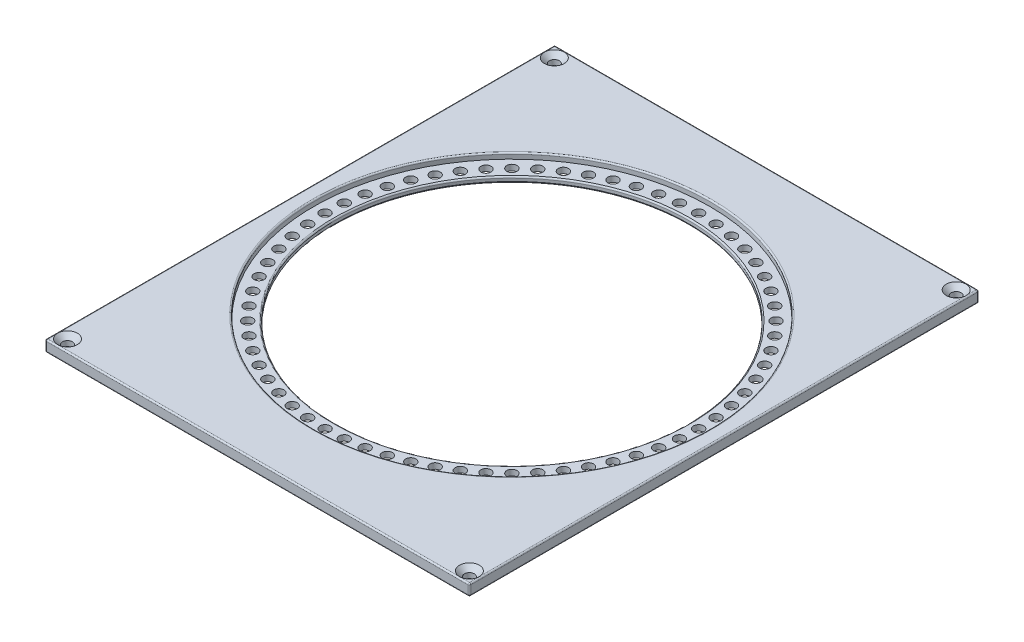
SolidWorks part; units mm, degrees
ref_plane "Front Plane" through (0, 0, 0) normal (0, 0, 1) x (1, 0, 0)
ref_plane "Top Plane" through (0, 0, 0) normal (0, 1, 0) x (1, 0, 0)
ref_plane "Right Plane" through (0, 0, 0) normal (1, 0, 0) x (0, 0, -1)
sketch "Sketch1" plane through (0, 0, 0) normal (0, 1, 0) x (1, 0, 0)
  line L0 (0, 0) -> (46.669, -46.669) construction
  line L1 (75, -90) -> (-75, -90)
  line L2 (75, -90) -> (75, 90)
  line L3 (75, 90) -> (-75, 90)
  line L4 (-75, -90) -> (-75, 90)
  line L5 (0, 90) -> (0, -90) construction
  line L6 (75, 0) -> (-75, 0) construction
  line L7 (0, 0) -> (36.6676, -54.877) construction
  line L8 (0, 0) -> (25.2571, -60.976) construction
  line L9 (0, 0) -> (12.876, -64.7318) construction
  line L10 (0, 0) -> (0, -66) construction
  line L11 (0, 0) -> (-12.876, -64.7318) construction
  line L12 (0, 0) -> (-25.2571, -60.976) construction
  line L13 (0, 0) -> (-36.6676, -54.877) construction
  line L14 (0, 0) -> (-46.669, -46.669) construction
  line L15 (0, 0) -> (-54.877, -36.6676) construction
  line L16 (0, 0) -> (-60.976, -25.2571) construction
  line L17 (0, 0) -> (-64.7318, -12.876) construction
  line L18 (0, 0) -> (-66, 0) construction
  line L19 (0, 0) -> (-64.7318, 12.876) construction
  line L20 (0, 0) -> (-60.976, 25.2571) construction
  line L21 (0, 0) -> (-54.877, 36.6676) construction
  line L22 (0, 0) -> (-46.669, 46.669) construction
  line L23 (0, 0) -> (-36.6676, 54.877) construction
  line L24 (0, 0) -> (-25.2571, 60.976) construction
  line L25 (0, 0) -> (-12.876, 64.7318) construction
  line L26 (0, 0) -> (0, 66) construction
  line L27 (0, 0) -> (12.876, 64.7318) construction
  line L28 (0, 0) -> (25.2571, 60.976) construction
  line L29 (0, 0) -> (36.6676, 54.877) construction
  line L30 (0, 0) -> (46.669, 46.669) construction
  line L31 (0, 0) -> (54.877, 36.6676) construction
  line L32 (0, 0) -> (60.976, 25.2571) construction
  line L33 (0, 0) -> (64.7318, 12.876) construction
  line L34 (0, 0) -> (66, 0) construction
  line L35 (0, 0) -> (64.7318, -12.876) construction
  line L36 (0, 0) -> (60.976, -25.2571) construction
  line L37 (0, 0) -> (54.877, -36.6676) construction
  line L38 (-75, 82) -> (-67, 82) construction
  line L39 (-67, 82) -> (-67, 90) construction
  line L40 (75, 82) -> (67, 82) construction
  line L41 (67, 82) -> (67, 90) construction
  line L42 (-75, -82) -> (-67, -82) construction
  line L43 (-67, -82) -> (-67, -90) construction
  line L44 (67, -90) -> (67, -82) construction
  line L45 (67, -82) -> (75, -82) construction
  line L46 (-67, 82) -> (-75, 90) construction
  line L47 (67, 82) -> (75, 90) construction
  line L48 (-67, -82) -> (-75, -90) construction
  line L49 (67, -82) -> (75, -90) construction
  line L50 (72.7, 87.7) -> (-72.7, 87.7) construction
  line L51 (46.669, -46.669) -> (42.4264, -42.4264) construction
  line L52 (-72.7, -87.7) -> (-72.7, 87.7) construction
  line L53 (72.7, -87.7) -> (-72.7, -87.7) construction
  line L54 (72.7, -87.7) -> (72.7, 87.7) construction
  line L55 (-72.7, 0) -> (-72.7, 10)
  line L56 (-72.7, 10) -> (-70.1478, 10)
  line L57 (-70.1478, 10) -> (-70.1478, -10)
  line L58 (-70.1478, -10) -> (-72.7, -10)
  line L59 (-72.7, -10) -> (-72.7, 0)
  line L60 (0, -87.7) -> (-10, -87.7)
  line L61 (-10, -87.7) -> (-10, -85.7)
  line L62 (-10, -85.7) -> (10, -85.7)
  line L63 (10, -85.7) -> (10, -87.7)
  line L64 (10, -87.7) -> (0, -87.7)
  line L65 (0, 87.7) -> (10, 87.7)
  line L66 (10, 87.7) -> (10, 85.7)
  line L67 (10, 85.7) -> (-10, 85.7)
  line L68 (-10, 85.7) -> (-10, 87.7)
  line L69 (-10, 87.7) -> (0, 87.7)
  circle A1 centre (0, 0) radius 62.5
  circle A2 centre (0, 0) radius 70
  circle A3 centre (46.669, -46.669) radius 1.5 construction
  circle A4 centre (46.669, -46.669) radius 1.8
  circle A5 centre (36.6676, -54.877) radius 1.8
  circle A6 centre (36.6676, -54.877) radius 1.5 construction
  circle A7 centre (25.2571, -60.976) radius 1.8
  circle A8 centre (25.2571, -60.976) radius 1.5 construction
  circle A9 centre (12.876, -64.7318) radius 1.8
  circle A10 centre (12.876, -64.7318) radius 1.5 construction
  circle A11 centre (0, -66) radius 1.8
  circle A12 centre (0, -66) radius 1.5 construction
  circle A13 centre (-12.876, -64.7318) radius 1.8
  circle A14 centre (-12.876, -64.7318) radius 1.5 construction
  circle A15 centre (-25.2571, -60.976) radius 1.8
  circle A16 centre (-25.2571, -60.976) radius 1.5 construction
  circle A17 centre (-36.6676, -54.877) radius 1.8
  circle A18 centre (-36.6676, -54.877) radius 1.5 construction
  circle A19 centre (-46.669, -46.669) radius 1.8
  circle A20 centre (-46.669, -46.669) radius 1.5 construction
  circle A21 centre (-54.877, -36.6676) radius 1.8
  circle A22 centre (-54.877, -36.6676) radius 1.5 construction
  circle A23 centre (-60.976, -25.2571) radius 1.8
  circle A24 centre (-60.976, -25.2571) radius 1.5 construction
  circle A25 centre (-64.7318, -12.876) radius 1.8
  circle A26 centre (-64.7318, -12.876) radius 1.5 construction
  circle A27 centre (-66, 0) radius 1.8
  circle A28 centre (-66, 0) radius 1.5 construction
  circle A29 centre (-64.7318, 12.876) radius 1.8
  circle A30 centre (-64.7318, 12.876) radius 1.5 construction
  circle A31 centre (-60.976, 25.2571) radius 1.8
  circle A32 centre (-60.976, 25.2571) radius 1.5 construction
  circle A33 centre (-54.877, 36.6676) radius 1.8
  circle A34 centre (-54.877, 36.6676) radius 1.5 construction
  circle A35 centre (-46.669, 46.669) radius 1.8
  circle A36 centre (-46.669, 46.669) radius 1.5 construction
  circle A37 centre (-36.6676, 54.877) radius 1.8
  circle A38 centre (-36.6676, 54.877) radius 1.5 construction
  circle A39 centre (-25.2571, 60.976) radius 1.8
  circle A40 centre (-25.2571, 60.976) radius 1.5 construction
  circle A41 centre (-12.876, 64.7318) radius 1.8
  circle A42 centre (-12.876, 64.7318) radius 1.5 construction
  circle A43 centre (0, 66) radius 1.8
  circle A44 centre (0, 66) radius 1.5 construction
  circle A45 centre (12.876, 64.7318) radius 1.8
  circle A46 centre (12.876, 64.7318) radius 1.5 construction
  circle A47 centre (25.2571, 60.976) radius 1.8
  circle A48 centre (25.2571, 60.976) radius 1.5 construction
  circle A49 centre (36.6676, 54.877) radius 1.8
  circle A50 centre (36.6676, 54.877) radius 1.5 construction
  circle A51 centre (46.669, 46.669) radius 1.8
  circle A52 centre (46.669, 46.669) radius 1.5 construction
  circle A53 centre (54.877, 36.6676) radius 1.8
  circle A54 centre (54.877, 36.6676) radius 1.5 construction
  circle A55 centre (60.976, 25.2571) radius 1.8
  circle A56 centre (60.976, 25.2571) radius 1.5 construction
  circle A57 centre (64.7318, 12.876) radius 1.8
  circle A58 centre (64.7318, 12.876) radius 1.5 construction
  circle A59 centre (66, 0) radius 1.8
  circle A60 centre (66, 0) radius 1.5 construction
  circle A61 centre (64.7318, -12.876) radius 1.8
  circle A62 centre (64.7318, -12.876) radius 1.5 construction
  circle A63 centre (60.976, -25.2571) radius 1.8
  circle A64 centre (60.976, -25.2571) radius 1.5 construction
  circle A65 centre (54.877, -36.6676) radius 1.8
  circle A66 centre (54.877, -36.6676) radius 1.5 construction
  circle A67 centre (-71, 86) radius 1.75
  circle A68 centre (71, 86) radius 1.75
  circle A69 centre (71, -86) radius 1.75
  circle A70 centre (-71, -86) radius 1.75
  circle A71 centre (41.87, -51.0187) radius 1.8
  circle A72 centre (36.6676, -54.877) radius 1.8
  circle A73 centre (31.1122, -58.2068) radius 1.8
  circle A74 centre (25.2571, -60.976) radius 1.8
  circle A75 centre (19.1588, -63.1581) radius 1.8
  circle A76 centre (12.876, -64.7318) radius 1.8
  circle A77 centre (6.4691, -65.6822) radius 1.8
  circle A78 centre (0, -66) radius 1.8
  circle A79 centre (-6.4691, -65.6822) radius 1.8
  circle A80 centre (-12.876, -64.7318) radius 1.8
  circle A81 centre (-19.1588, -63.1581) radius 1.8
  circle A82 centre (-25.2571, -60.976) radius 1.8
  circle A83 centre (-31.1122, -58.2068) radius 1.8
  circle A84 centre (-36.6676, -54.877) radius 1.8
  circle A85 centre (-41.87, -51.0187) radius 1.8
  circle A86 centre (-46.669, -46.669) radius 1.8
  circle A87 centre (-51.0187, -41.87) radius 1.8
  circle A88 centre (-54.877, -36.6676) radius 1.8
  circle A89 centre (-58.2068, -31.1122) radius 1.8
  circle A90 centre (-60.976, -25.2571) radius 1.8
  circle A91 centre (-63.1581, -19.1588) radius 1.8
  circle A92 centre (-64.7318, -12.876) radius 1.8
  circle A93 centre (-65.6822, -6.4691) radius 1.8
  circle A94 centre (-66, 0) radius 1.8
  circle A95 centre (-65.6822, 6.4691) radius 1.8
  circle A96 centre (-64.7318, 12.876) radius 1.8
  circle A97 centre (-63.1581, 19.1588) radius 1.8
  circle A98 centre (-60.976, 25.2571) radius 1.8
  circle A99 centre (-58.2068, 31.1122) radius 1.8
  circle A100 centre (-54.877, 36.6676) radius 1.8
  circle A101 centre (-51.0187, 41.87) radius 1.8
  circle A102 centre (-46.669, 46.669) radius 1.8
  circle A103 centre (-41.87, 51.0187) radius 1.8
  circle A104 centre (-36.6676, 54.877) radius 1.8
  circle A105 centre (-31.1122, 58.2068) radius 1.8
  circle A106 centre (-25.2571, 60.976) radius 1.8
  circle A107 centre (-19.1588, 63.1581) radius 1.8
  circle A108 centre (-12.876, 64.7318) radius 1.8
  circle A109 centre (-6.4691, 65.6822) radius 1.8
  circle A110 centre (0, 66) radius 1.8
  circle A111 centre (6.4691, 65.6822) radius 1.8
  circle A112 centre (12.876, 64.7318) radius 1.8
  circle A113 centre (19.1588, 63.1581) radius 1.8
  circle A114 centre (25.2571, 60.976) radius 1.8
  circle A115 centre (31.1122, 58.2068) radius 1.8
  circle A116 centre (36.6676, 54.877) radius 1.8
  circle A117 centre (41.87, 51.0187) radius 1.8
  circle A118 centre (46.669, 46.669) radius 1.8
  circle A119 centre (51.0187, 41.87) radius 1.8
  circle A120 centre (54.877, 36.6676) radius 1.8
  circle A121 centre (58.2068, 31.1122) radius 1.8
  circle A122 centre (60.976, 25.2571) radius 1.8
  circle A123 centre (63.1581, 19.1588) radius 1.8
  circle A124 centre (64.7318, 12.876) radius 1.8
  circle A125 centre (65.6822, 6.4691) radius 1.8
  circle A126 centre (66, 0) radius 1.8
  circle A127 centre (65.6822, -6.4691) radius 1.8
  circle A128 centre (64.7318, -12.876) radius 1.8
  circle A129 centre (63.1581, -19.1588) radius 1.8
  circle A130 centre (60.976, -25.2571) radius 1.8
  circle A131 centre (58.2068, -31.1122) radius 1.8
  circle A132 centre (54.877, -36.6676) radius 1.8
  circle A133 centre (51.0187, -41.87) radius 1.8
  point P140 (0, 0)
  point P291 (0, 0)
  dimension "D3" = 140
  dimension "D6" = 3
  dimension "D12" = 3.5
  dimension "D2" = 125
  dimension "D4" = 66
  dimension "D5" = 45
  dimension "D9" = 180
  dimension "D10" = 150
  dimension "D11" = 8
  dimension "D15" = 2.5522
  dimension "D16" = 20
  dimension "D17" = 2
  dimension "D18" = 20
  dimension "D19" = 2
  dimension "D20" = 20
  dimension "D7" = 0.3
  dimension "D14" = 2.3
  dimension "D8" = 32
  dimension "D13" = 64
extrude "Boss-Extrude1" add sketch "Sketch1" along normal blind 2 contours A1 A65 A63 A61 A59 A57 A55 A53 A51 A49 A47 A45 A43 A41 A39 A37 A35 A33 A31 A29 A27 A25 A23 A21 A19 A17 region at (-68.0201, 0, 0)
extrude "Boss-Extrude2" add sketch "Sketch1<3>" along normal blind 4 contours L4 L1 L2 L3 A70 A69 A68 A67 A2 L58 L59 L55 L56 L57 L63 L64 L60 L61 L62 L68 L69 L65 L66 L67 | L57 L58 L59 L55 L56 | L62 L63 L64 L60 L61 | L67 L68 L69 L65 L66 region at (0, 0, 89.7657)
sketch "Sketch1<3>" plane through (0, 0, 0) normal (0, 1, 0) x (1, 0, 0) same geometry as "Sketch1"
sketch "Sketch2" plane through (-75, 0, 0) normal (-1, 0, 0) x (0, 0, 1)
  line L1 (-90, 4) -> (90, 4)
  line L2 (-90, 4) -> (-90, 0)
  line L3 (-90, 0) -> (90, 0)
  line L4 (90, 4) -> (90, 0)
extrude "Cut-Extrude1" cut sketch "Sketch2" against normal blind 0.1
chamfer "Chamfer1" distance 1.75 angle 45 4 edges at (71, 4, 87.75) (71, 4, -84.25) (-71, 4, -84.25) (-71, 4, 87.75)
extrude "Boss-Extrude3" add sketch "Sketch1<4>" against normal blind 2 contours L67 L68 L69 L65 L66 | L59 L55 L56 L57 L58 | L60 L61 L62 L63 L64
sketch "Sketch1<4>" plane through (0, 0, 0) normal (0, 1, 0) x (1, 0, 0) same geometry as "Sketch1"
fillet "Fillet1" radius 0.5 31 edges at (-71, 0, -84.25) (71, 0, -84.25) (71, 0, 87.75) (-71, 0, 87.75) (0.05, 0, -90) (75, 2, -90) (75, 0, 0) (75, 2, 90) (0.05, 0, 90) (0.05, 4, -90) (75, 4, 0) (0.05, 4, 90) (0, 4, 70) (0, 0, 62.5) (0, 2, 62.5) (-74.9, 0, 0) (-74.9, 2, -90) (-74.9, 2, 90) (-74.9, 4, 0) (10, -2, 86.7) (0, -2, 85.7) (-10, -2, 86.7) (0, -2, 87.7) (-70.1478, -2, 0) (-71.4239, -2, -10) (-72.7, -2, 0) (-71.4239, -2, 10) (0, -2, -87.7) (-10, -2, -86.7) (0, -2, -85.7) (10, -2, -86.7)
